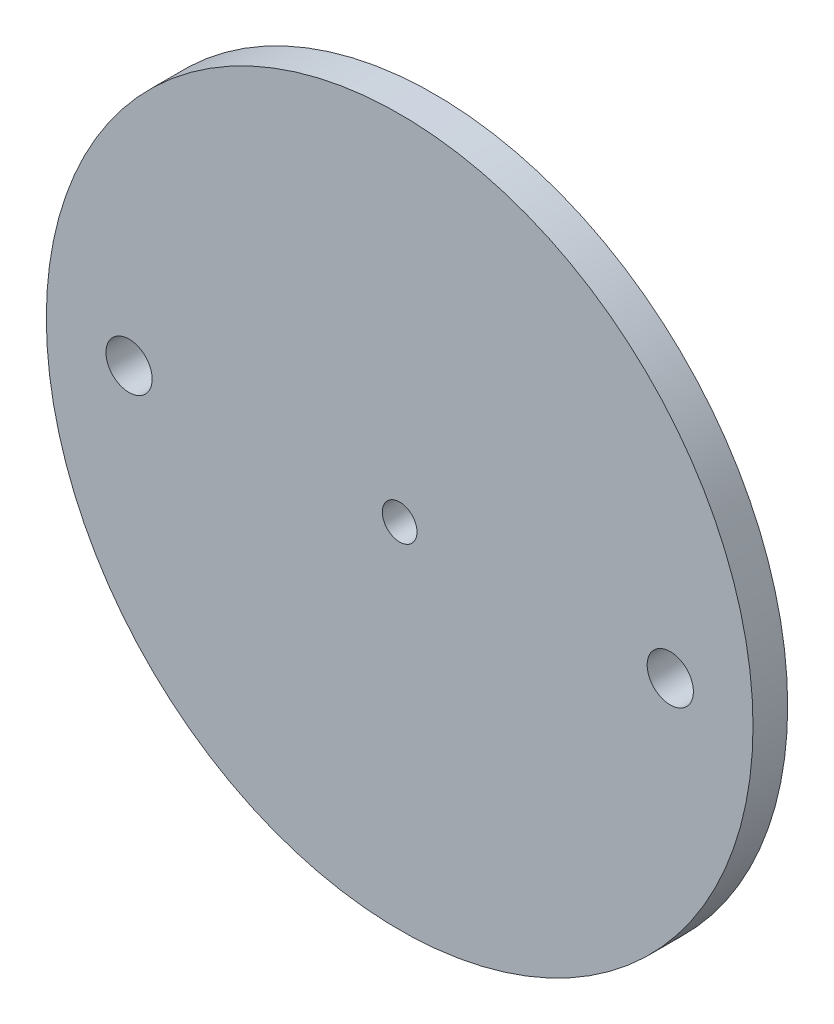
SolidWorks part; units mm, degrees
material "E-Glass Fiber"
ref_plane "Front Plane" through (0, 0, 0) normal (0, 0, 1) x (1, 0, 0)
ref_plane "Top Plane" through (0, 0, 0) normal (0, 1, 0) x (1, 0, 0)
ref_plane "Right Plane" through (0, 0, 0) normal (1, 0, 0) x (0, 0, -1)
sketch "Sketch1" plane through (0, 0, 0) normal (0, 0, 1) x (1, 0, 0)
  circle A0 centre (0, 0) radius 48.5394
  dimension "D1" = 97.0788
extrude "Boss-Extrude1" add sketch "Sketch1" along normal blind 4.7625
sketch "Sketch2" plane through (0, 0, 4.7625) normal (0, 0, 1) x (1, 0, 0)
  line L0 (-37.1729, 0) -> (0, 0) construction
  line L1 (0, 0) -> (37.1729, 0) construction
  circle A0 centre (0, 0) radius 2.3812
  circle A1 centre (37.1729, 0) radius 3.175
  circle A2 centre (-37.1729, 0) radius 3.175
  dimension "D1" = 4.7625
  dimension "D3" = 6.35
  dimension "D2" = 74.3458
extrude "Cut-Extrude1" cut sketch "Sketch2" against normal through all
